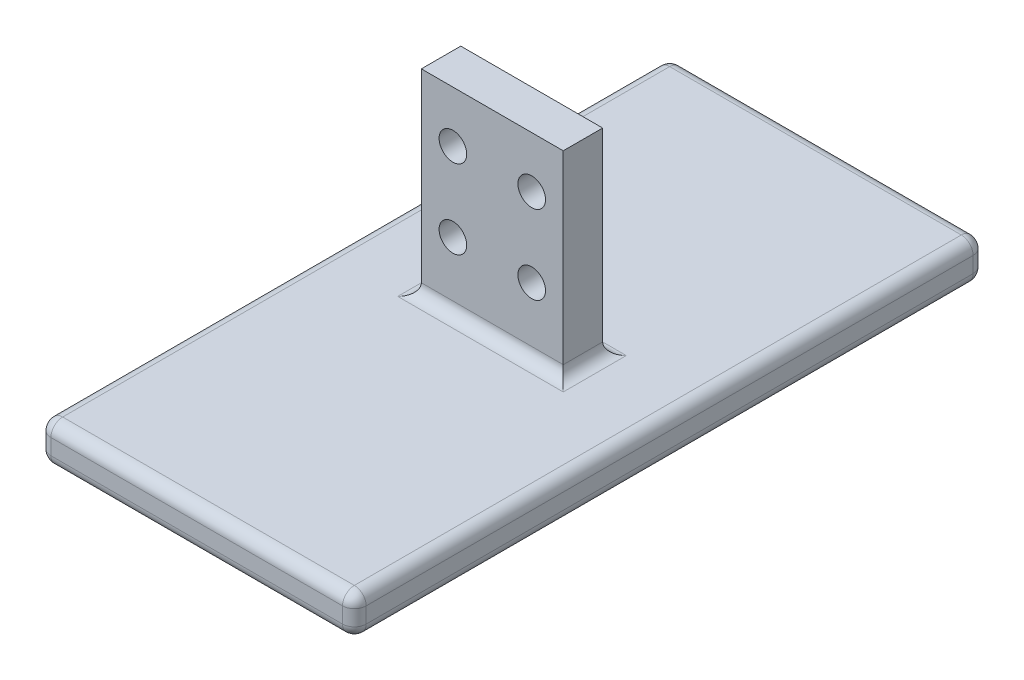
SolidWorks part; units mm, degrees
ref_plane "Front Plane" through (0, 0, 0) normal (0, 0, 1) x (1, 0, 0)
ref_plane "Top Plane" through (0, 0, 0) normal (0, 1, 0) x (1, 0, 0)
ref_plane "Right Plane" through (0, 0, 0) normal (1, 0, 0) x (0, 0, -1)
sketch "Sketch1" plane through (0, 0, 0) normal (0, 0, 1) x (1, 0, 0)
  line L1 (-20, 2.5) -> (20, 2.5)
  line L2 (-20, 2.5) -> (-20, -2.5)
  line L3 (-20, -2.5) -> (20, -2.5)
  line L4 (20, 2.5) -> (20, -2.5)
  line L5 (-20, 2.5) -> (20, -2.5) construction
  line L6 (-20, -2.5) -> (20, 2.5) construction
  point P0 (0, 0)
  dimension "D1" = 40
  dimension "D2" = 5
extrude "Boss-Extrude1" add sketch "Sketch1" along normal blind 40 and the other way blind 40
sketch "Sketch2" plane through (0, 0, 0) normal (0, 0, 1) x (1, 0, 0)
  line L0 (20, 2.5) -> (-20, 2.5) construction
  line L1 (-9, 27.5) -> (9, 27.5)
  line L2 (-9, 27.5) -> (-9, 2.5)
  line L3 (-9, 2.5) -> (9, 2.5)
  line L4 (9, 27.5) -> (9, 2.5)
  line L5 (-9, 27.5) -> (9, 2.5) construction
  line L6 (-9, 2.5) -> (9, 27.5) construction
  circle A0 centre (-5, 11) radius 1.75
  circle A1 centre (5, 11) radius 1.75
  circle A2 centre (5, 21) radius 1.75
  circle A3 centre (-5, 21) radius 1.75
  point P0 (0, 15)
  dimension "D3" = 3.5
  dimension "D1" = 18
  dimension "D2" = 25
  dimension "D4" = 4
  dimension "D5" = 4
  dimension "D6" = 8.5
  dimension "D7" = 10
extrude "Boss-Extrude2" add sketch "Sketch2" along normal blind 2.5 and the other way blind 2.5
fillet "Fillet1" radius 1.5 12 edges at (0, 2.5, 2.5) (9, 2.5, 0) (0, 2.5, -2.5) (-9, 2.5, 0) (0, 2.5, -40) (20, 2.5, 0) (0, 2.5, 40) (-20, 2.5, 0) (0, -2.5, -40) (-20, -2.5, 0) (0, -2.5, 40) (20, -2.5, 0)
fillet "Fillet2" radius 1.5 6 edges at (19.5607, -2.0607, 39.5607) (19.5607, 2.0607, 39.5607) (-19.5607, 2.0607, 39.5607) (-19.5607, -2.0607, 39.5607) (20, 0, 40) (-20, 0, 40)
fillet "Fillet3" radius 1.5 6 edges at (19.5607, -2.0607, -39.5607) (19.5607, 2.0607, -39.5607) (-19.5607, 2.0607, -39.5607) (-19.5607, -2.0607, -39.5607) (20, 0, -40) (-20, 0, -40)
